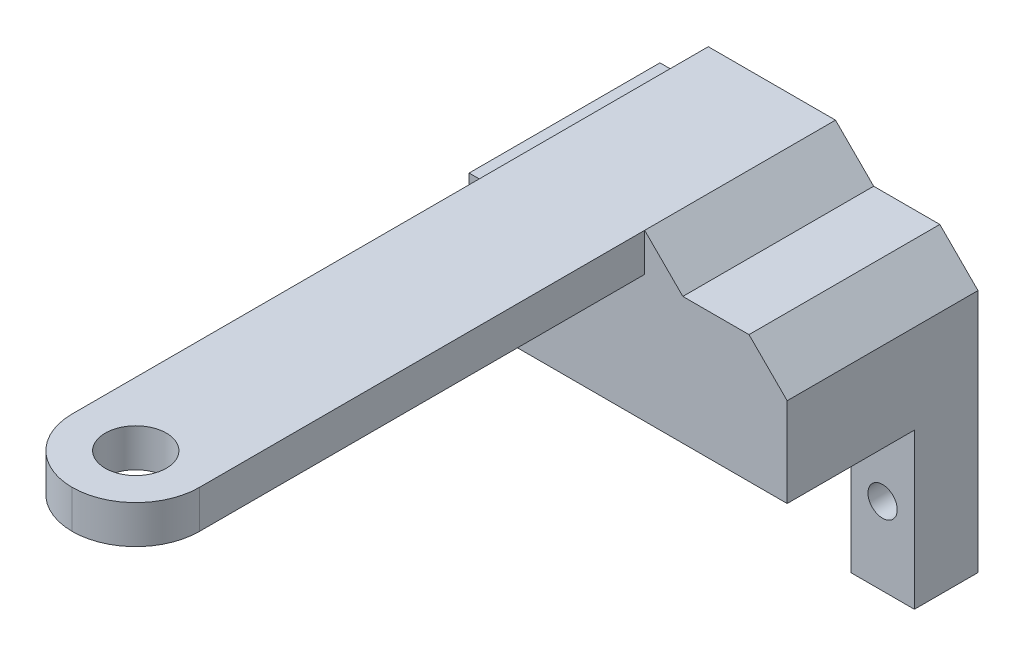
SolidWorks part; units mm, degrees
ref_plane "Front Plane" through (0, 0, 0) normal (0, 0, 1) x (1, 0, 0)
ref_plane "Top Plane" through (0, 0, 0) normal (0, 1, 0) x (1, 0, 0)
ref_plane "Right Plane" through (0, 0, 0) normal (1, 0, 0) x (0, 0, -1)
sketch "Sketch1" plane through (0, 0, 0) normal (0, 1, 0) x (1, 0, 0)
  line L0 (0, 0) -> (50000, 0) construction
  line L1 (11.2, 0) -> (16.2, 0)
  line L2 (11.2, 0) -> (11.2, -5)
  line L3 (11.2, -5) -> (16.2, -5)
  line L4 (16.2, 0) -> (16.2, -5)
  dimension "D1" = 5
  dimension "D2" = 11.2
extrude "servo mount" add sketch "Sketch1" against normal blind 12.2
sketch "Sketch2" plane through (0, 0, 0) normal (0, 0, -1) x (-1, 0, 0)
  line L0 (-16.2, -6.1) -> (-11.2, -6.1) construction
  line L1 (-16.2, -12.2) -> (-16.2, 0) construction
  line L2 (-11.2, -12.2) -> (-11.2, 0) construction
  circle A0 centre (-13.7, -6.1) radius 1.15
  dimension "D1" = 2.3
extrude "servo mount screw hole" cut sketch "Sketch2" against normal up to next
sketch "Sketch3" plane through (0, 0, 0) normal (0, 1, 0) x (1, 0, 0)
  line L0 (0, 0) -> (0, 50000) construction
  line L1 (16.2, 0) -> (-8.8, 0)
  line L2 (16.2, 0) -> (16.2, -15)
  line L3 (16.2, -15) -> (-8.8, -15)
  line L4 (-8.8, 0) -> (-8.8, -15)
  dimension "D1" = 25
  dimension "D2" = 15
extrude "servo retaining plate" add sketch "Sketch3" along normal blind 10
sketch "Sketch5" plane through (0, 10, 0) normal (0, 1, 0) x (1, 0, 0)
  line L0 (0, 0) -> (0, 50000) construction
  line L1 (-8.8, -15) -> (16.2, -15) construction
  line L2 (-5, 0) -> (5, 0)
  line L3 (-5, 0) -> (-5, -55)
  line L4 (-5, -55) -> (5, -55)
  line L5 (5, 0) -> (5, -55)
  line L6 (16.2, 0) -> (-8.8, 0) construction
  point P7 (0, 0)
  dimension "D1" = 10
  dimension "D2" = 40
extrude "neck" add sketch "Sketch5" along normal blind 3
fillet "neck fillet1" radius 5 2 edges at (5, 11.5, 55) (-5, 11.5, 55)
sketch "Sketch6" plane through (0, 13, 0) normal (0, 1, 0) x (1, 0, 0)
  line L0 (-5, -50) -> (5, -50) construction
  circle A0 centre (0, -50) radius 2.4
  dimension "D1" = 4.8
extrude "lower servo mount hole" cut sketch "Sketch6" against normal up to next
chamfer "Chamfer1" distance 3 angle 45 3 edges at (16.2, 10, 7.5) (-5, 10, 7.5) (5, 10, 7.5)
equation "\"D2@Sketch1\"=22.4mm/2"
